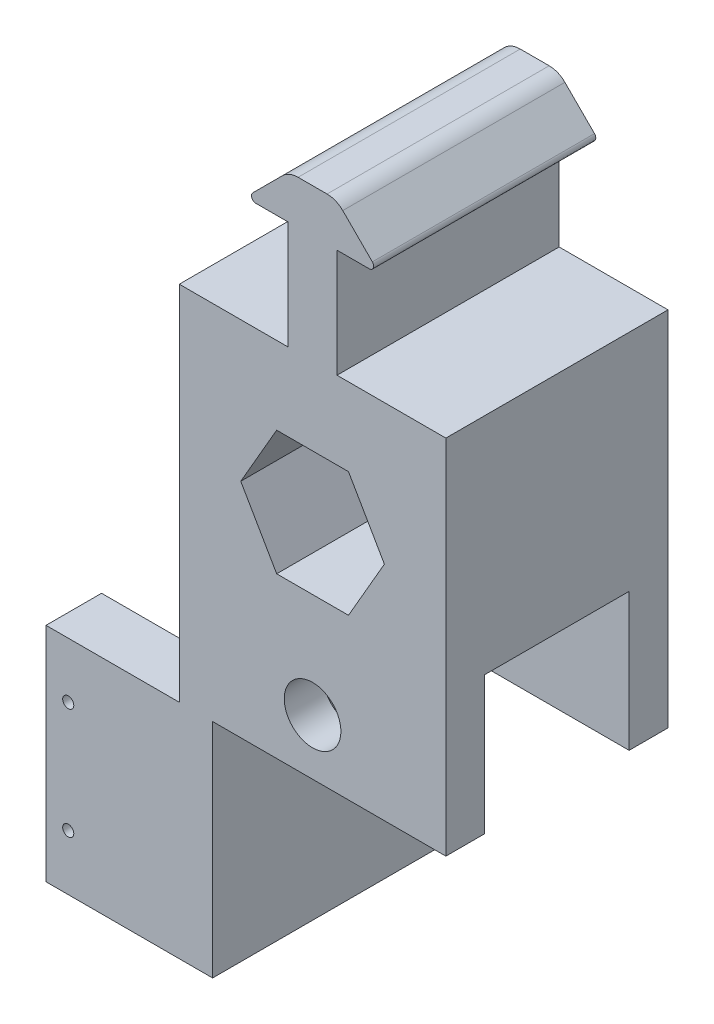
SolidWorks part; units mm, degrees
ref_plane "Front Plane" through (0, 0, 0) normal (0, 0, 1) x (1, 0, 0)
ref_plane "Top Plane" through (0, 0, 0) normal (0, 1, 0) x (1, 0, 0)
ref_plane "Right Plane" through (0, 0, 0) normal (1, 0, 0) x (0, 0, -1)
sketch "Sketch1" plane through (0, 0, 0) normal (0, 0, 1) x (1, 0, 0)
  line L0 (-15.24, 16.002) -> (-15.24, -25.4)
  line L1 (-4.1061, 7.112) -> (-8.2122, 0)
  line L2 (-8.2122, 0) -> (-4.1061, -7.112)
  line L3 (-4.1061, -7.112) -> (4.1061, -7.112)
  line L4 (4.1061, -7.112) -> (8.2122, 0)
  line L5 (8.2122, 0) -> (4.1061, 7.112)
  line L6 (4.1061, 7.112) -> (-4.1061, 7.112)
  line L7 (-15.24, -25.4) -> (15.24, -25.4)
  line L8 (15.24, -25.4) -> (15.24, 16.002)
  line L9 (-15.24, 16.002) -> (-2.794, 16.002)
  line L10 (-2.794, 16.002) -> (-2.794, 28.3845)
  line L11 (-2.794, 28.3845) -> (-6.477, 28.3845)
  line L12 (-6.8362, 29.2517) -> (-3.4525, 32.6355)
  line L13 (-1.6564, 33.3794) -> (1.6564, 33.3794)
  line L14 (0, 41.8096) -> (0, -25.778) construction
  line L15 (15.24, 16.002) -> (2.794, 16.002)
  line L16 (2.794, 16.002) -> (2.794, 28.3845)
  line L17 (6.8362, 29.2517) -> (3.4525, 32.6355)
  line L18 (2.794, 28.3845) -> (6.477, 28.3845)
  line L19 (-6.985, 28.8925) -> (6.985, 28.8925) construction
  circle A0 centre (0, 0) radius 7.112 construction
  arc A1 (-6.477, 28.3845) -> (-6.8362, 29.2517) centre (-6.477, 28.8925) cw
  arc A2 (-3.4525, 32.6355) -> (-1.6564, 33.3794) centre (-1.6564, 30.8394) cw
  arc A3 (3.4525, 32.6355) -> (1.6564, 33.3794) centre (1.6564, 30.8394) ccw
  arc A4 (6.477, 28.3845) -> (6.8362, 29.2517) centre (6.477, 28.8925) ccw
  point P18 (7.7034, 28.3845)
  point P21 (-4.6355, 28.3845)
  point P25 (-7.7034, 28.3845)
  point P29 (0, -25.4)
  point P35 (0, 33.3794)
  dimension "D7" = 0.508
  dimension "D8" = 2.54
  dimension "D1" = 14.224
  dimension "D2" = 21.2725
  dimension "D3" = 5.588
  dimension "D4" = 4.9949
  dimension "D5" = 135
  dimension "D6" = 13.97
  dimension "D9" = 25.4
  dimension "D10" = 8.89
  dimension "D11" = 15.24
extrude "Boss-Extrude1" add sketch "Sketch1" along normal mid plane 25.4
sketch "Sketch10" plane through (0, 0, 0) normal (0, 0, 1) x (1, 0, 0)
  line L0 (-15.24, -25.4) -> (-15.24, -46.99)
  line L1 (-15.24, -46.99) -> (-30.48, -46.99)
  line L2 (-30.48, -46.99) -> (-30.48, -50.8)
  line L3 (-30.48, -50.8) -> (-11.43, -50.8)
  line L4 (-11.43, -50.8) -> (-11.43, -25.4)
  line L5 (-15.24, -25.4) -> (15.24, -25.4) construction
  line L6 (-15.24, -25.4) -> (-11.43, -25.4)
  dimension "D1" = 19.05
  dimension "D2" = 21.59
  dimension "D3" = 3.81
extrude "Boss-Extrude4" add sketch "Sketch10" along normal up to surface and the other way up to surface up to face at (0, 19.8373, 12.7) other way up to face at (0, 19.8373, -12.7)
sketch "Sketch6" plane through (15.24, 0, 0) normal (1, 0, 0) x (0, 0, -1)
  line L0 (-12.7, -7.112) -> (12.7, -7.112) construction
  line L1 (-12.7, -7.112) -> (12.7, -7.112) construction
  line L2 (-8.255, -25.4) -> (-8.255, -9.652)
  line L3 (-8.255, -9.652) -> (8.255, -9.652)
  line L11 (-8.255, -25.4) -> (8.255, -25.4)
  line L12 (8.255, -9.652) -> (8.255, -25.4)
  point P10 (0, -9.652)
  dimension "D2" = 16.51
  dimension "D3" = 2.54
  dimension "D1" = 15.748
extrude "Cut-Extrude2" cut sketch "Sketch6" against normal through all
sketch "Sketch11" plane through (0, -46.99, 0) normal (0, 1, 0) x (1, 0, 0)
  line L0 (-30.48, -12.7) -> (-30.48, 12.7) construction
  line L1 (-15.24, -12.7) -> (-15.24, 12.7) construction
  line L2 (-30.48, -3.81) -> (-30.48, 3.81)
  line L3 (-15.24, -3.81) -> (-15.24, 3.81)
  line L4 (-30.48, 3.81) -> (-15.24, 3.81)
  line L5 (-30.48, -3.81) -> (-15.24, -3.81)
  point P8 (-15.24, 0)
  point P9 (-30.48, 0)
  dimension "D1" = 7.62
extrude "Cut-Extrude3" cut sketch "Sketch11" against normal up to surface (3.81 mm away) up to face at (-20.955, -50.8, 0)
sketch "Sketch15" plane through (0, 0, 12.7) normal (0, 0, 1) x (1, 0, 0)
  line L1 (-4.1061, -7.112) -> (4.1061, -7.112) construction
  circle A0 centre (0, -19.05) radius 3.2385
  point P7 (0, -7.112)
  dimension "D1" = 6.477
  dimension "D2" = 11.938
extrude "Cut-Extrude4" cut sketch "Sketch15" against normal up to surface (25.4 mm away) up to face at (-4.191, 6.0908, -12.7)
sketch "Sketch16" plane through (-15.24, 0, 0) normal (-1, 0, 0) x (0, 0, 1)
  line L0 (12.7, -46.99) -> (3.81, -46.99) construction
  line L1 (-3.81, -46.99) -> (-12.7, -46.99) construction
  line L2 (12.7, -46.99) -> (6.35, -46.99)
  line L3 (-6.35, -46.99) -> (-12.7, -46.99)
  line L4 (-12.7, -46.99) -> (-12.7, -25.4)
  line L5 (-12.7, 16.002) -> (-12.7, -46.99) construction
  line L6 (-12.7, -25.4) -> (-6.35, -25.4)
  line L7 (-6.35, -25.4) -> (-6.35, -46.99)
  line L8 (6.35, -46.99) -> (6.35, -25.4)
  line L9 (6.35, -25.4) -> (12.7, -25.4)
  line L10 (12.7, 16.002) -> (12.7, -46.99) construction
  line L11 (12.7, -25.4) -> (12.7, -46.99)
  line L12 (8.255, -25.4) -> (-8.255, -25.4) construction
  dimension "D1" = 6.35
extrude "Boss-Extrude5" add sketch "Sketch16" along normal blind 15.24
sketch "Sketch17" plane through (0, 0, 12.7) normal (0, 0, 1) x (1, 0, 0)
  line L0 (-30.48, -25.4) -> (-15.24, -25.4) construction
  circle A0 centre (-27.94, -31.75) radius 0.635
  circle A1 centre (-27.94, -44.45) radius 0.635
  point P5 (0, 0)
  dimension "D3" = 1.27
  dimension "D1" = 12.7
  dimension "D2" = 12.7
  dimension "D4" = 6.35
extrude "Cut-Extrude5" cut sketch "Sketch17" against normal through all
